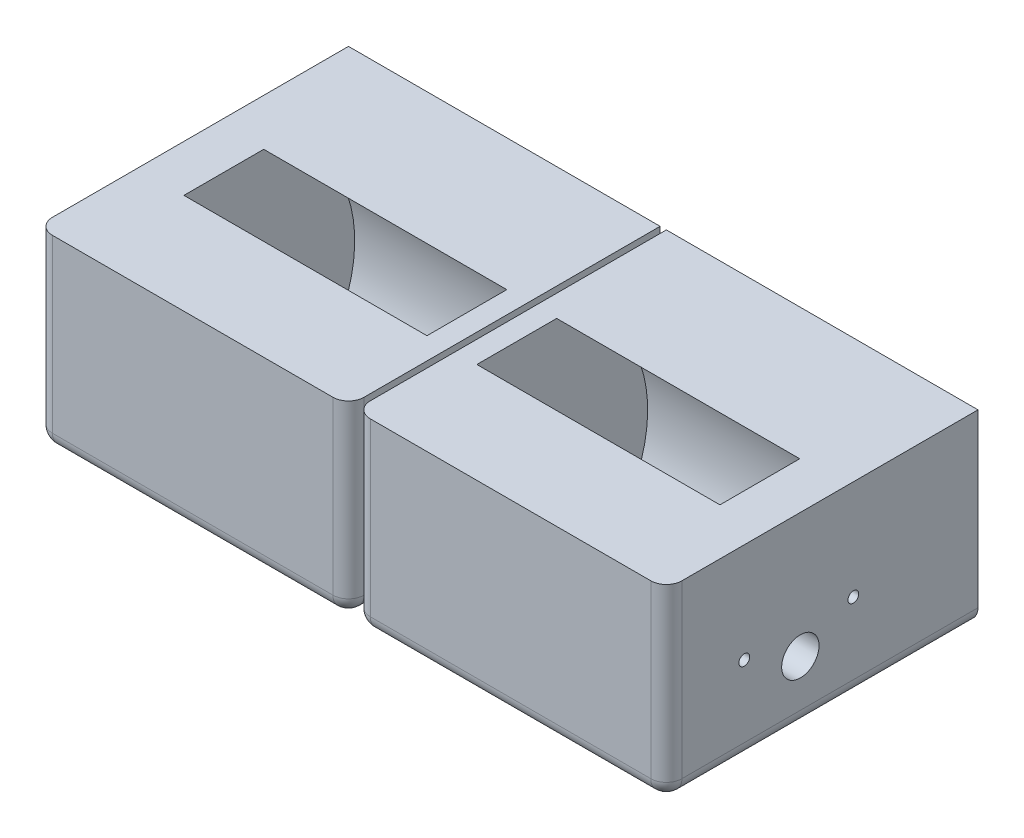
SolidWorks part; units mm, degrees
ref_plane "Front Plane" through (0, 0, 0) normal (0, 0, 1) x (1, 0, 0)
ref_plane "Top Plane" through (0, 0, 0) normal (0, 1, 0) x (1, 0, 0)
ref_plane "Right Plane" through (0, 0, 0) normal (1, 0, 0) x (0, 0, -1)
sketch "Sketch1" plane through (0, 0, 0) normal (0, 0, 1) x (1, 0, 0)
  line L0 (-50, -30) -> (50, -30)
  line L1 (-50, -30) -> (-50, 30)
  line L2 (50, -30) -> (50, 30)
  line L3 (-50, 30) -> (50, 30)
  line L4 (-50, -30) -> (50, 30) construction
  line L5 (50, -30) -> (-50, 30) construction
  point P1 (0, 0)
extrude "Boss-Extrude1" add sketch "Sketch1" along normal blind 100 contours L3 L2 L0 L1
sketch3d "3DSketch1"
  line L2 (50, -30, 100) -> (50, -30, 0) construction
  line L3 (50, -30, 55) -> (50, 30, 55) construction
  line L4 (50, 30, 100) -> (50, 30, 0) construction
  line L5 (50, 30, 55) -> (-50, 30, 55) construction
  line L6 (-50, 30, 100) -> (-50, 30, 0) construction
  line L7 (-50, -10, 55) -> (-35, -10, 55) construction
  line L8 (-50, -30, 100) -> (-50, -30, 0) construction
  line L9 (-50, -30, 55) -> (50, -30, 55) construction
  line L10 (-50, -30, 55) -> (-50, -10, 55) construction
  circle A0 centre (-35, -10, 55) radius 42
  circle A1 centre (-35, -10, 55) radius 2.1
  point P18 (7, -10, 55)
  point P20 (-32.9, -10, 55)
extrude "Cut-Extrude3" cut sketch "3DSketch1" along direction (1, 0, 0) on the side against the normal blind 78 contours A0
sketch3d "3DSketch2"
  line L0 (40, -30, 55) -> (50, -30, 55) construction
  line L1 (-35, -10, 55) -> (-35, -10, 57) construction
  line L3 (50, -30, 55) -> (50, 30, 55) construction
  line L5 (50, 30, 55) -> (-50, 30, 55) construction
  line L7 (-50, -10, 55) -> (-35, -10, 55) construction
  line L9 (-50, -30, 55) -> (50, -30, 55) construction
  line L10 (-50, -30, 55) -> (-50, -10, 55) construction
  circle A0 centre (-35, -10, 57) radius 2.5
  point P3 (-32.5, -10, 57)
extrude "Cut-Extrude4" cut sketch "3DSketch2" along direction (1, 0, 0) on the side against the normal through all both and the other way through all contours A0
sketch "Sketch3" plane through (-50, 0, 0) normal (-1, 0, 0) x (0, 0, 1)
  circle A0 centre (57, -10) radius 6
extrude "Cut-Extrude5" cut sketch "Sketch3" against normal up to next
sketch "Sketch4" plane through (-50, 0, 0) normal (-1, 0, 0) x (0, 0, 1)
  line L0 (57, -2) -> (40, -2) construction
  line L1 (57, -2) -> (75, -2) construction
  line L3 (57, -10) -> (57, -2) construction
hole_wizard "Tap Drill for #8-32 Tap1" positions "Sketch6" profile "Sketch5" hole size "#8-32" standard "ANSI Inch"
sketch "Sketch6" plane through (-50, 0, 0) normal (-1, 0, 0) x (0, 0, 1)
  point P0 (75, -2)
  point P3 (40, -2)
sketch "Sketch5" plane through (-50, -2, 75) normal (0, 1, 0) x (0, 0, 1)
  line L0 (0, 0) -> (0, 21.0378)
  line L1 (0, 21.0378) -> (1.7272, 20)
  line L2 (1.7272, 20) -> (1.7272, 0)
  line L5 (1.7272, 0) -> (0, 0)
  line L10 (0, 21.0378) -> (-1.7272, 20) construction
  line L11 (0, -6.35) -> (0, 107.95) construction
  dimension "Hole Dia." = 3.4544
  dimension "Hole Depth" = 20
  dimension "Drill Angle" = 118
sketch "Sketch7" plane through (43, 0, 0) normal (-1, 0, 0) x (0, 0, 1)
  circle A0 centre (57, -10) radius 6
extrude "Cut-Extrude6" cut sketch "Sketch7" against normal blind 2 and the other way blind 80
sketch "Sketch8" plane through (0, -30, 0) normal (0, -1, 0) x (1, 0, 0)
  line L0 (-35, 91.9324) -> (43, 91.9324) construction
  line L1 (4, 91.9324) -> (4, 100) construction
  line L2 (-50, 100) -> (50, 100) construction
  line L3 (-3.5, 94.4662) -> (11.5, 94.4662)
  line L4 (-3.5, 94.4662) -> (-3.5, 97.4662)
  line L5 (11.5, 94.4662) -> (11.5, 97.4662)
  line L6 (-3.5, 97.4662) -> (11.5, 97.4662)
  line L7 (-3.5, 94.4662) -> (11.5, 97.4662) construction
  line L8 (11.5, 94.4662) -> (-3.5, 97.4662) construction
  point P9 (4, 95.9662)
extrude "Cut-Extrude7" cut sketch "Sketch8" against normal blind 5
sketch "Sketch9" plane through (0, -30, 0) normal (0, -1, 0) x (-1, 0, 0)
  line L0 (35, -91.9324) -> (-43, -91.9324) construction
  line L1 (3.5, -94.4662) -> (-11.5, -94.4662)
  line L2 (3.5, -94.4662) -> (3.5, -91.9324)
  line L3 (3.5, -91.9324) -> (-11.5, -91.9324)
  line L4 (-11.5, -94.4662) -> (-11.5, -91.9324)
extrude "Cut-Extrude8" cut sketch "Sketch9" against normal blind 1.5
fillet "Fillet1" radius 5 5 edges at (0, -30, 100) (50, -30, 50) (-50, -30, 50) (50, 0, 100) (-50, 0, 100)
ref_plane "Plane1" through (51, 0, 0) normal (1, 0, 0) x (0, 0, -1)
mirror "Mirror5" about plane through (51, 0, 0) normal (1, 0, 0) of bodies 112
